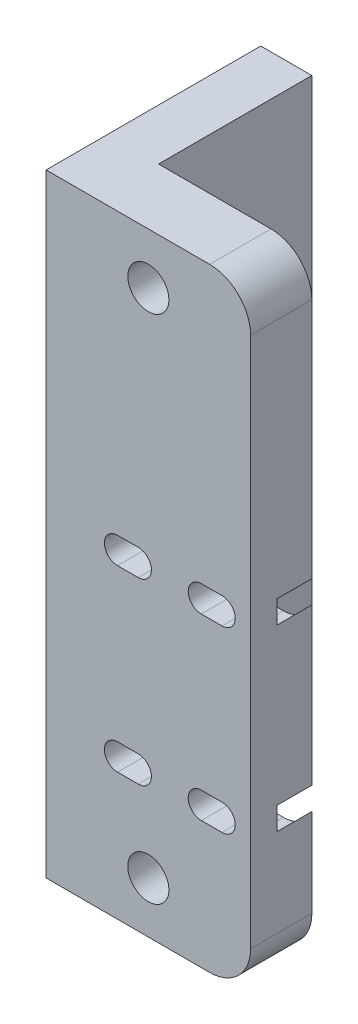
SolidWorks part; units mm, degrees
ref_plane "Front Plane" through (0, 0, 0) normal (0, 0, 1) x (1, 0, 0)
ref_plane "Top Plane" through (0, 0, 0) normal (0, 1, 0) x (1, 0, 0)
ref_plane "Right Plane" through (0, 0, 0) normal (1, 0, 0) x (0, 0, -1)
sketch "Sketch1" plane through (0, 0, 0) normal (0, 0, 1) x (1, 0, 0)
  line L1 (-12.7, 38.1) -> (12.7, 38.1)
  line L2 (-12.7, 38.1) -> (-12.7, -38.1)
  line L3 (-12.7, -38.1) -> (12.7, -38.1)
  line L4 (12.7, 38.1) -> (12.7, -38.1)
  dimension "D1" = 76.2
  dimension "D2" = 25.4
  dimension "D3" = 12.7
  dimension "D4" = 38.1
extrude "Boss-Extrude1" add sketch "Sketch1" along normal blind 7.62
hole_wizard "#10 Clearance Hole1" positions "Sketch3" profile "Sketch2" hole size "#10" standard "ANSI Inch"
sketch "Sketch3" plane through (0, 0, 7.62) normal (0, 0, 1) x (1, 0, 0)
  line L1 (12.7, -38.1) -> (12.7, 38.1) construction
  line L2 (12.7, 38.1) -> (-12.7, 38.1) construction
  point P0 (0, 31.75)
  point P2 (0, -31.75)
  point P14 (0, 38.1)
  dimension "D1" = 6.35
  dimension "D2" = 63.5
  dimension "D3" = 12.7
  dimension "D4" = 12.7
sketch "Sketch2" plane through (0, 31.75, 7.62) normal (1, 0, 0) x (0, -1, 0)
  line L0 (0, 0) -> (0, 26.9338)
  line L1 (0, 26.9338) -> (2.5527, 25.4)
  line L2 (2.5527, 25.4) -> (2.5527, 0)
  line L5 (2.5527, 0) -> (0, 0)
  line L10 (0, 26.9338) -> (-2.5527, 25.4) construction
  line L11 (0, -6.35) -> (0, 107.95) construction
  dimension "Hole Dia." = 5.1054
  dimension "Hole Depth" = 25.4
  dimension "Drill Angle" = 118
hole_wizard "CBORE SLOT for #4 Socket Head Cap Screw1" positions "Sketch6" profile "Sketch5" size "#4" standard "ANSI Inch" slot yes end condition through all
sketch "Sketch6" plane through (-2.0173, -3.8136, 0) normal (0, 0, 1) x (1, 0, 0)
  line L1 (-10.6827, 41.9136) -> (-10.6827, -34.2864) construction
  line L2 (-3.4437, 5.4011) -> (2.3983, 5.4011) construction
  circle A1 centre (2.0173, -27.9364) radius 2.5527 construction
  point P0 (-0.5227, 5.4011)
  point P2 (-0.5227, -16.8239)
  point P4 (9.8913, -16.8239)
  point P6 (9.8913, 5.4011)
  dimension "D1" = 22.225
  dimension "D2" = 10.414
  dimension "D3" = 11.1125
  dimension "D4" = 10.16
  dimension "D5" = 5.842
sketch "Sketch5" plane through (-2.54, 1.5875, 0) normal (1, 0, 0) x (0, 1, 0)
  line L0 (0, 0) -> (0, 7.62)
  line L1 (0, 7.62) -> (1.632, 7.62)
  line L3 (1.632, 7.62) -> (1.6319, 4.318)
  line L4 (1.6319, 4.318) -> (3.81, 4.318)
  line L5 (3.81, 4.318) -> (3.81, 0)
  line L7 (3.81, 0) -> (0, 0)
  line L11 (0, -6.35) -> (0, 107.95) construction
  dimension "Thru Hole Dia." = 3.2639
  dimension "Thru Hole Depth" = 7.62
  dimension "C'Bore Dia." = 7.62
  dimension "C'Bore Depth" = 4.318
fillet "Fillet1" radius 5.08 2 edges at (12.7, 38.1, 3.81) (12.7, -38.1, 3.81)
sketch "Sketch7" plane through (0, 38.1, 0) normal (0, 1, 0) x (1, 0, 0)
  line L0 (-2.54, -7.62) -> (-2.54, 4.38)
  line L1 (7.62, -7.62) -> (-12.7, -7.62) construction
  line L2 (7.62, 0) -> (-12.7, 0) construction
  dimension "D1" = 12
  dimension "D2" = 4.38
sketch "Sketch8" plane through (0, 0, 0) normal (0, 0, -1) x (-1, 0, 0)
  line L13 (12.7, -38.1) -> (-7.62, -38.1) construction
  line L14 (12.7, 38.1) -> (6.35, 38.1)
  line L15 (12.7, 38.1) -> (12.7, -38.1)
  line L16 (12.7, -38.1) -> (6.35, -38.1)
  line L17 (6.35, 38.1) -> (6.35, -38.1)
  dimension "D1" = 6.35
extrude "Boss-Extrude2" add sketch "Sketch8" along normal blind 19.05
